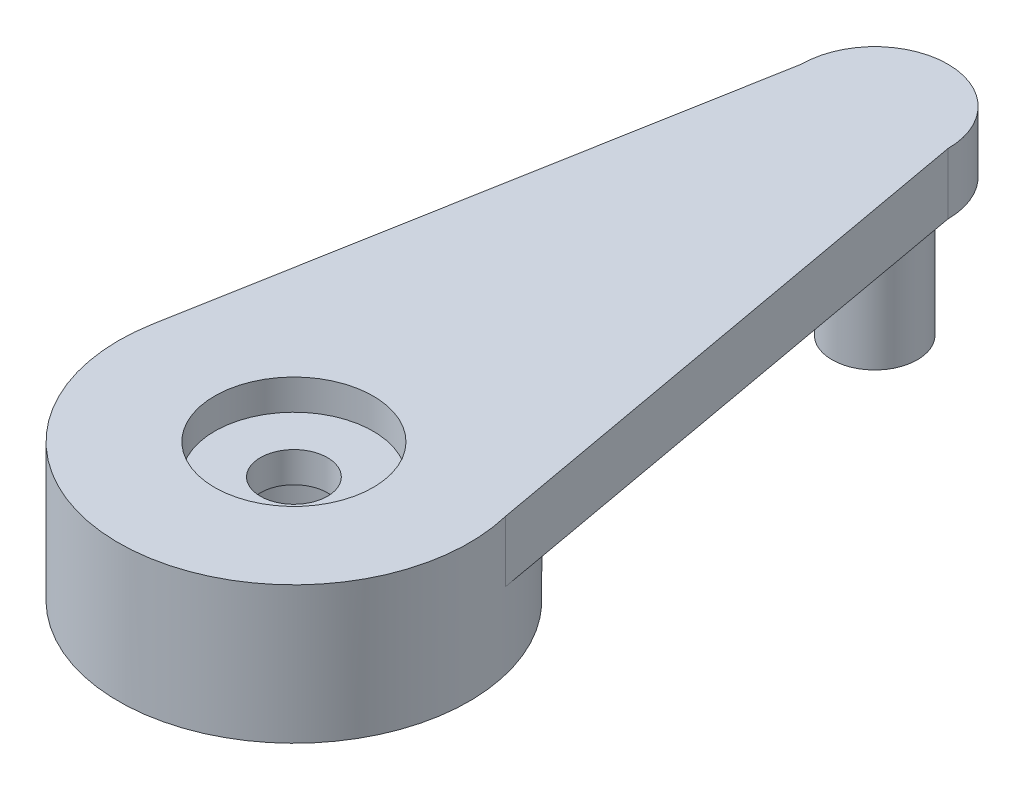
SolidWorks part; units mm, degrees
ref_plane "Front Plane" through (0, 0, 0) normal (0, 0, 1) x (1, 0, 0)
ref_plane "Top Plane" through (0, 0, 0) normal (0, 1, 0) x (1, 0, 0)
ref_plane "Right Plane" through (0, 0, 0) normal (1, 0, 0) x (0, 0, -1)
sketch "Sketch1" plane through (0, 0, 0) normal (0, 1, 0) x (1, 0, 0)
  line L0 (34.3744, -12.5965) -> (31.1177, -30.6246)
  line L1 (39.1744, -12.5965) -> (42.4853, -30.9628)
  circle A5 centre (36.7744, -12.5965) radius 1.4
  circle A6 centre (36.7761, -31.6468) radius 2.6
  circle A7 centre (36.7761, -31.6468) radius 5.75
  circle A8 centre (36.7744, -12.5965) radius 2.4
  circle A9 centre (36.7761, -31.6468) radius 1.1
extrude "Boss-Extrude1" add sketch "Sketch1" along normal blind 2 contours A8 L0 A7 L1 | A8 A5 | A5 | A9 | A6 A9 | A7 region at (36.7709, 0, 21.2507) region at (36.7744, 0, 10.2644) region at (36.7744, 0, 12.5965) region at (34.2496, 0, 31.6468) region at (36.7761, 0, 31.6468)
extrude "Boss-Extrude2" add sketch "Sketch1<4>" along normal blind 1 contours A6 A9 region at (34.2496, 0, 31.6468)
sketch "Sketch1<4>" plane through (0, 0, 0) normal (0, 1, 0) x (1, 0, 0) same geometry as "Sketch1"
extrude "Boss-Extrude5" add sketch "Sketch1<6>" against normal blind 4.5 contours A5 region at (36.7744, 0, 12.5965)
sketch "Sketch1<6>" plane through (0, 0, 0) normal (0, 1, 0) x (1, 0, 0) same geometry as "Sketch1"
sketch "Sketch3" plane through (0, 0, 0) normal (0, -1, 0) x (1, 0, 0)
  circle A0 centre (36.7761, 31.6468) radius 1.1
  circle A1 centre (36.7761, 31.6468) radius 5.75
  circle A2 centre (36.7761, 31.6468) radius 2.6
  arc M6 (42.3647, 30.2941) -> (31.1177, 30.6246) centre (36.7761, 31.6468) ccw
extrude "Boss-Extrude6" add sketch "Sketch3" along normal blind 2.5 contours A1 A2 M6 region at (42.3241, 0, 30.9849)
